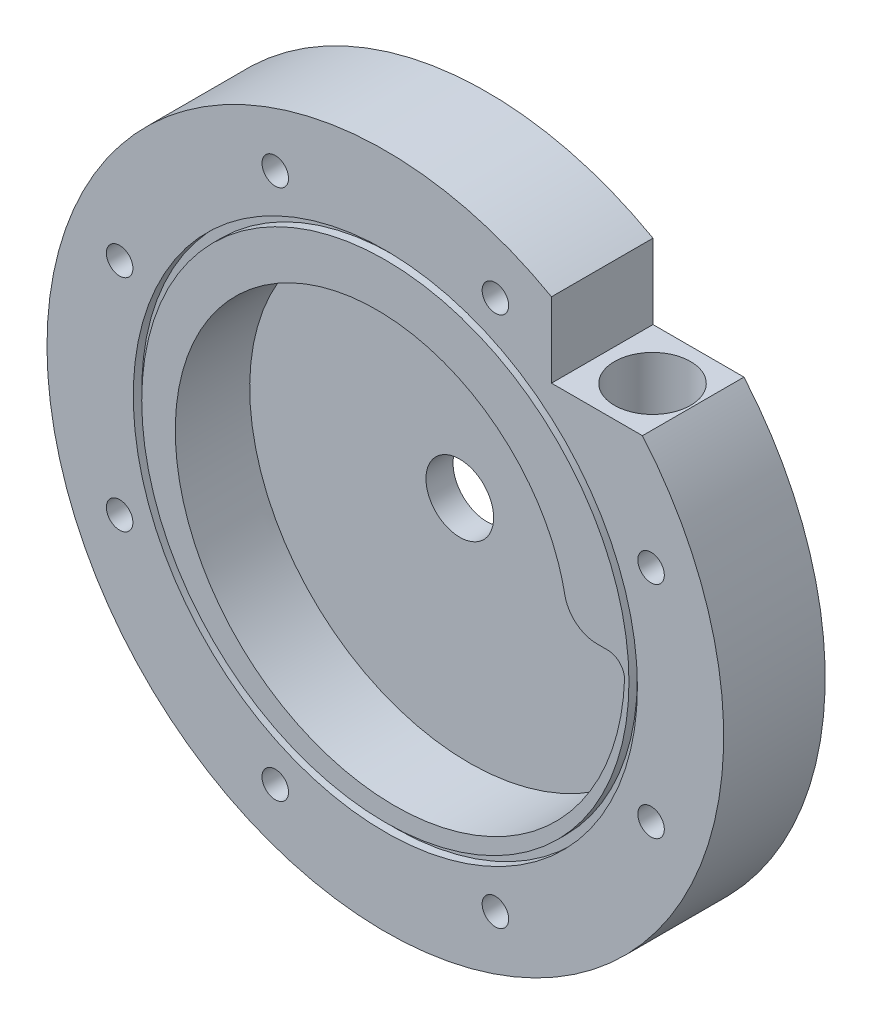
SolidWorks part; units mm, degrees
note: The reader was unsure of these and kept them because the rebuilt part matched: shared geometry of "Sketch1<3>".
material "6061-T6 (SS)"
ref_plane "Front Plane" through (0, 0, 0) normal (0, 0, 1) x (1, 0, 0)
ref_plane "Top Plane" through (0, 0, 0) normal (0, 1, 0) x (1, 0, 0)
ref_plane "Right Plane" through (0, 0, 0) normal (1, 0, 0) x (0, 0, -1)
curve "Volute Spiral"
sketch "Sketch1" plane through (0, 0, 0) normal (0, 0, 1) x (1, 0, 0)
  line L3 (39.6934, 3.175) -> (41.7237, 3.175)
  circle A0 centre (0, 0) radius 63.5
  arc A1 (36.5184, 0) -> (39.6934, 3.175) centre (39.6934, 0) cw
  arc A2 (41.7237, 3.175) -> (44.8987, 0) centre (41.7237, 0) cw
  circle A3 centre (0, 0) radius 6.35
  arc A4 (34.2959, 0) -> (36.5184, 0) centre (35.4071, 0) ccw
  spline S0 degree 3 poles (2030.2227, -117.7395) (22.7858, -27.2351) (33.8418, -13.6396) (34.312, 0.4316) (34.3179, 0.6476) (34.3271, 1.0799) (34.3329, 2.0903) (34.2799, 3.6074) (34.1204, 5.4103) (33.8802, 7.1353) (33.5529, 8.8499) (33.139, 10.5497) (32.6391, 12.2303) (32.0542, 13.8874) (31.3852, 15.5166) (30.6335, 17.1136) (29.8006, 18.6744) (28.8882, 20.1947) (27.8984, 21.6706) (26.8332, 23.098) (25.6951, 24.4731) (24.4865, 25.7922) (23.2102, 27.0516) (21.8693, 28.248) (20.4667, 29.3779) (19.0058, 30.4382) (17.49, 31.4258) (15.9229, 32.338) (14.3083, 33.1721) (12.6501, 33.9256) (10.9523, 34.5962) (9.219, 35.1819) (7.4546, 35.6807) (5.6632, 36.091) (3.8495, 36.4113) (2.0178, 36.6406) (0.1728, 36.7776) (-1.6809, 36.8217) (-3.5386, 36.7724) (-5.3955, 36.6294) (-7.2471, 36.3925) (-9.0884, 36.0621) (-10.9149, 35.6384) (-12.7217, 35.1223) (-14.5042, 34.5145) (-16.2577, 33.8162) (-17.9777, 33.0288) (-19.6596, 32.1539) (-21.2989, 31.1934) (-22.8914, 30.1492) (-24.4326, 29.0238) (-25.9186, 27.8195) (-27.3451, 26.5392) (-28.7085, 25.1857) (-30.0048, 23.7622) (-31.2305, 22.2719) (-32.3822, 20.7185) (-33.4566, 19.1055) (-34.4506, 17.4368) (-35.3613, 15.7165) (-36.1861, 13.9486) (-36.9225, 12.1375) (-37.5682, 10.2875) (-38.1211, 8.4034) (-38.5795, 6.4896) (-38.9418, 4.5509) (-39.2066, 2.5922) (-39.3728, 0.6184) (-39.4396, -1.3656) (-39.4064, -3.3547) (-39.2728, -5.3439) (-39.0387, -7.3282) (-38.7043, -9.3025) (-38.27, -11.2616) (-37.7365, -13.2006) (-37.1047, -15.1144) (-36.3758, -16.9979) (-35.5512, -18.8464) (-34.6327, -20.6549) (-33.6221, -22.4187) (-32.5217, -24.133) (-31.3338, -25.7933) (-30.0611, -27.3951) (-28.7065, -28.9341) (-27.273, -30.4061) (-25.7641, -31.807) (-24.1833, -33.133) (-22.5341, -34.3804) (-20.8206, -35.5457) (-19.0469, -36.6255) (-17.2172, -37.6168) (-15.3359, -38.5166) (-13.4077, -39.3222) (-11.4371, -40.0312) (-9.4292, -40.6415) (-7.3888, -41.1509) (-5.3209, -41.5579) (-3.2309, -41.8608) (-1.1238, -42.0586) (0.9951, -42.1502) (3.1203, -42.135) (5.2464, -42.0126) (7.3682, -41.7828) (9.4801, -41.4458) (11.5767, -41.002) (13.6527, -40.4521) (15.7025, -39.7969) (17.721, -39.0379) (19.7028, -38.1764) (21.6428, -37.2142) (23.5358, -36.1534) (25.3768, -34.9962) (27.1608, -33.7453) (28.8832, -32.4033) (30.5392, -30.9734) (32.1244, -29.4588) (33.6345, -27.8631) (35.0652, -26.19) (36.4127, -24.4433) (37.6731, -22.6273) (38.8428, -20.7464) (39.9186, -18.8049) (40.8973, -16.8077) (41.776, -14.7596) (42.552, -12.6656) (43.223, -10.5308) (43.7868, -8.3606) (44.2416, -6.1602) (44.5713, -4.0283) (44.7406, -2.4408) (44.8137, -1.5038) (44.8395, -1.1283) (44.857, -0.8465) (44.8728, -0.5645) (45.7077, 16.1379) (34.8318, 33.2748) (2044.1391, -40.8845) knots -0.167612 -0.167612 -0.167612 -0.167612 0.00087 0.001741 0.002611 0.003482 0.006969 0.014827 0.021828 0.028845 0.035878 0.042927 0.049991 0.057071 0.064166 0.071278 0.078405 0.085549 0.092709 0.099884 0.107076 0.114284 0.121508 0.128748 0.136004 0.143277 0.150566 0.157872 0.165193 0.172531 0.179886 0.187257 0.194645 0.202049 0.209469 0.216906 0.22436 0.231831 0.239318 0.246821 0.254342 0.261879 0.269433 0.277004 0.284591 0.292196 0.299817 0.307455 0.31511 0.322782 0.330471 0.338177 0.3459 0.35364 0.361397 0.369171 0.376962 0.38477 0.392595 0.400438 0.408298 0.416174 0.424069 0.43198 0.439908 0.447854 0.455817 0.463798 0.471796 0.479811 0.487843 0.495893 0.503961 0.512046 0.520148 0.528268 0.536405 0.54456 0.552732 0.560922 0.569129 0.577354 0.585596 0.593857 0.602135 0.61043 0.618743 0.627074 0.635423 0.643789 0.652173 0.660575 0.668994 0.677432 0.685887 0.69436 0.702851 0.71136 0.719886 0.728431 0.736993 0.745574 0.754172 0.762788 0.771423 0.780075 0.788745 0.797433 0.80614 0.814864 0.823607 0.832367 0.841146 0.849943 0.858758 0.867591 0.876443 0.885312 0.8942 0.903106 0.91203 0.920973 0.929933 0.938912 0.94791 0.956925 0.965959 0.975011 0.984082 0.992034 0.994309 0.995446 0.996584 0.997723 0.998861 1.198776 1.198776 1.198776 1.198776 only from (34.2959, 0) to (44.8987, 0) construction
  spline S1 degree 3 poles (34.2959, 0) (34.2988, 0.0719) (34.3048, 0.2158) (34.312, 0.4316) (34.3179, 0.6476) (34.3271, 1.0799) (34.3329, 2.0903) (34.2799, 3.6074) (34.1204, 5.4103) (33.8802, 7.1353) (33.5529, 8.8499) (33.139, 10.5497) (32.6391, 12.2303) (32.0542, 13.8874) (31.3852, 15.5166) (30.6335, 17.1136) (29.8006, 18.6744) (28.8882, 20.1947) (27.8984, 21.6706) (26.8332, 23.098) (25.6951, 24.4731) (24.4865, 25.7922) (23.2102, 27.0516) (21.8693, 28.248) (20.4667, 29.3779) (19.0058, 30.4382) (17.49, 31.4258) (15.9229, 32.338) (14.3083, 33.1721) (12.6501, 33.9256) (10.9523, 34.5962) (9.219, 35.1819) (7.4546, 35.6807) (5.6632, 36.091) (3.8495, 36.4113) (2.0178, 36.6406) (0.1728, 36.7776) (-1.6809, 36.8217) (-3.5386, 36.7724) (-5.3955, 36.6294) (-7.2471, 36.3925) (-9.0884, 36.0621) (-10.9149, 35.6384) (-12.7217, 35.1223) (-14.5042, 34.5145) (-16.2577, 33.8162) (-17.9777, 33.0288) (-19.6596, 32.1539) (-21.2989, 31.1934) (-22.8914, 30.1492) (-24.4326, 29.0238) (-25.9186, 27.8195) (-27.3451, 26.5392) (-28.7085, 25.1857) (-30.0048, 23.7622) (-31.2305, 22.2719) (-32.3822, 20.7185) (-33.4566, 19.1055) (-34.4506, 17.4368) (-35.3613, 15.7165) (-36.1861, 13.9486) (-36.9225, 12.1375) (-37.5682, 10.2875) (-38.1211, 8.4034) (-38.5795, 6.4896) (-38.9418, 4.5509) (-39.2066, 2.5922) (-39.3728, 0.6184) (-39.4396, -1.3656) (-39.4064, -3.3547) (-39.2728, -5.3439) (-39.0387, -7.3282) (-38.7043, -9.3025) (-38.27, -11.2616) (-37.7365, -13.2006) (-37.1047, -15.1144) (-36.3758, -16.9979) (-35.5512, -18.8464) (-34.6327, -20.6549) (-33.6221, -22.4187) (-32.5217, -24.133) (-31.3338, -25.7933) (-30.0611, -27.3951) (-28.7065, -28.9341) (-27.273, -30.4061) (-25.7641, -31.807) (-24.1833, -33.133) (-22.5341, -34.3804) (-20.8206, -35.5457) (-19.0469, -36.6255) (-17.2172, -37.6168) (-15.3359, -38.5166) (-13.4077, -39.3222) (-11.4371, -40.0312) (-9.4292, -40.6415) (-7.3888, -41.1509) (-5.3209, -41.5579) (-3.2309, -41.8608) (-1.1238, -42.0586) (0.9951, -42.1502) (3.1203, -42.135) (5.2464, -42.0126) (7.3682, -41.7828) (9.4801, -41.4458) (11.5767, -41.002) (13.6527, -40.4521) (15.7025, -39.7969) (17.721, -39.0379) (19.7028, -38.1764) (21.6428, -37.2142) (23.5358, -36.1534) (25.3768, -34.9962) (27.1608, -33.7453) (28.8832, -32.4033) (30.5392, -30.9734) (32.1244, -29.4588) (33.6345, -27.8631) (35.0652, -26.19) (36.4127, -24.4433) (37.6731, -22.6273) (38.8428, -20.7464) (39.9186, -18.8049) (40.8973, -16.8077) (41.776, -14.7596) (42.552, -12.6656) (43.223, -10.5308) (43.7868, -8.3606) (44.2416, -6.1602) (44.5713, -4.0283) (44.7406, -2.4408) (44.8137, -1.5038) (44.8395, -1.1283) (44.857, -0.8465) (44.8728, -0.5645) (44.8869, -0.2823) (44.8948, -0.0941) (44.8987, 0) knots 0 0 0 0 0.00087 0.001741 0.002611 0.003482 0.006969 0.014827 0.021828 0.028845 0.035878 0.042927 0.049991 0.057071 0.064166 0.071278 0.078405 0.085549 0.092709 0.099884 0.107076 0.114284 0.121508 0.128748 0.136004 0.143277 0.150566 0.157872 0.165193 0.172531 0.179886 0.187257 0.194645 0.202049 0.209469 0.216906 0.22436 0.231831 0.239318 0.246821 0.254342 0.261879 0.269433 0.277004 0.284591 0.292196 0.299817 0.307455 0.31511 0.322782 0.330471 0.338177 0.3459 0.35364 0.361397 0.369171 0.376962 0.38477 0.392595 0.400438 0.408298 0.416174 0.424069 0.43198 0.439908 0.447854 0.455817 0.463798 0.471796 0.479811 0.487843 0.495893 0.503961 0.512046 0.520148 0.528268 0.536405 0.54456 0.552732 0.560922 0.569129 0.577354 0.585596 0.593857 0.602135 0.61043 0.618743 0.627074 0.635423 0.643789 0.652173 0.660575 0.668994 0.677432 0.685887 0.69436 0.702851 0.71136 0.719886 0.728431 0.736993 0.745574 0.754172 0.762788 0.771423 0.780075 0.788745 0.797433 0.80614 0.814864 0.823607 0.832367 0.841146 0.849943 0.858758 0.867591 0.876443 0.885312 0.8942 0.903106 0.91203 0.920973 0.929933 0.938912 0.94791 0.956925 0.965959 0.975011 0.984082 0.992034 0.994309 0.995446 0.996584 0.997723 0.998861 1 1 1 1
  dimension "D2" = 127
  dimension "D3" = 3.175
  dimension "D5" = 12.7
  dimension "D1" = 2.2225
extrude "Walls" add sketch "Sketch1" along normal blind 9.0729
extrude "Floor" add sketch "Sketch1<3>" against normal blind 5.08
sketch "Sketch1<3>" plane through (0, 0, 0) normal (0, 0, 1) x (1, 0, 0) same geometry as "Sketch1"
sketch "Sketch4" plane through (0, 0, -5.08) normal (0, 0, -1) x (-1, 0, 0)
  circle A0 centre (0, 0) radius 63.5
  circle A1 centre (0, 0) radius 60.325
  circle A2 centre (0, 0) radius 63.5 construction
  dimension "D1" = 3.175
ref_plane "Total Thickness" through (0, 0, 13.97) normal (0, 0, -1) x (-1, 0, 0)
sketch "Sketch5" plane through (0, 0, 9.0729) normal (0, 0, 1) x (1, 0, 0)
  line L2 (39.6934, 3.175) -> (41.7237, 3.175) construction
  line L3 (39.6934, 3.175) -> (41.7237, 3.175)
  arc A0 (44.8987, 0) -> (41.7237, 3.175) centre (41.7237, 0) ccw construction
  arc A1 (44.8987, 0) -> (41.7237, 3.175) centre (41.7237, 0) ccw
  arc A2 (33.6876, 8.1232) -> (39.6934, 3.175) centre (39.6934, 9.2938) ccw
  spline S0 degree 3 poles (2030.2227, -117.7395) (22.7858, -27.2351) (33.8418, -13.6396) (34.312, 0.4316) (34.3179, 0.6476) (34.3271, 1.0799) (34.3329, 2.0903) (34.2799, 3.6074) (34.1204, 5.4103) (33.8802, 7.1353) (33.5529, 8.8499) (33.139, 10.5497) (32.6391, 12.2303) (32.0542, 13.8874) (31.3852, 15.5166) (30.6335, 17.1136) (29.8006, 18.6744) (28.8882, 20.1947) (27.8984, 21.6706) (26.8332, 23.098) (25.6951, 24.4731) (24.4865, 25.7922) (23.2102, 27.0516) (21.8693, 28.248) (20.4667, 29.3779) (19.0058, 30.4382) (17.49, 31.4258) (15.9229, 32.338) (14.3083, 33.1721) (12.6501, 33.9256) (10.9523, 34.5962) (9.219, 35.1819) (7.4546, 35.6807) (5.6632, 36.091) (3.8495, 36.4113) (2.0178, 36.6406) (0.1728, 36.7776) (-1.6809, 36.8217) (-3.5386, 36.7724) (-5.3955, 36.6294) (-7.2471, 36.3925) (-9.0884, 36.0621) (-10.9149, 35.6384) (-12.7217, 35.1223) (-14.5042, 34.5145) (-16.2577, 33.8162) (-17.9777, 33.0288) (-19.6596, 32.1539) (-21.2989, 31.1934) (-22.8914, 30.1492) (-24.4326, 29.0238) (-25.9186, 27.8195) (-27.3451, 26.5392) (-28.7085, 25.1857) (-30.0048, 23.7622) (-31.2305, 22.2719) (-32.3822, 20.7185) (-33.4566, 19.1055) (-34.4506, 17.4368) (-35.3613, 15.7165) (-36.1861, 13.9486) (-36.9225, 12.1375) (-37.5682, 10.2875) (-38.1211, 8.4034) (-38.5795, 6.4896) (-38.9418, 4.5509) (-39.2066, 2.5922) (-39.3728, 0.6184) (-39.4396, -1.3656) (-39.4064, -3.3547) (-39.2728, -5.3439) (-39.0387, -7.3282) (-38.7043, -9.3025) (-38.27, -11.2616) (-37.7365, -13.2006) (-37.1047, -15.1144) (-36.3758, -16.9979) (-35.5512, -18.8464) (-34.6327, -20.6549) (-33.6221, -22.4187) (-32.5217, -24.133) (-31.3338, -25.7933) (-30.0611, -27.3951) (-28.7065, -28.9341) (-27.273, -30.4061) (-25.7641, -31.807) (-24.1833, -33.133) (-22.5341, -34.3804) (-20.8206, -35.5457) (-19.0469, -36.6255) (-17.2172, -37.6168) (-15.3359, -38.5166) (-13.4077, -39.3222) (-11.4371, -40.0312) (-9.4292, -40.6415) (-7.3888, -41.1509) (-5.3209, -41.5579) (-3.2309, -41.8608) (-1.1238, -42.0586) (0.9951, -42.1502) (3.1203, -42.135) (5.2464, -42.0126) (7.3682, -41.7828) (9.4801, -41.4458) (11.5767, -41.002) (13.6527, -40.4521) (15.7025, -39.7969) (17.721, -39.0379) (19.7028, -38.1764) (21.6428, -37.2142) (23.5358, -36.1534) (25.3768, -34.9962) (27.1608, -33.7453) (28.8832, -32.4033) (30.5392, -30.9734) (32.1244, -29.4588) (33.6345, -27.8631) (35.0652, -26.19) (36.4127, -24.4433) (37.6731, -22.6273) (38.8428, -20.7464) (39.9186, -18.8049) (40.8973, -16.8077) (41.776, -14.7596) (42.552, -12.6656) (43.223, -10.5308) (43.7868, -8.3606) (44.2416, -6.1602) (44.5713, -4.0283) (44.7406, -2.4408) (44.8137, -1.5038) (44.8395, -1.1283) (44.857, -0.8465) (44.8728, -0.5645) (45.7077, 16.1379) (34.8318, 33.2748) (2044.1391, -40.8845) knots -0.167612 -0.167612 -0.167612 -0.167612 0.00087 0.001741 0.002611 0.003482 0.006969 0.014827 0.021828 0.028845 0.035878 0.042927 0.049991 0.057071 0.064166 0.071278 0.078405 0.085549 0.092709 0.099884 0.107076 0.114284 0.121508 0.128748 0.136004 0.143277 0.150566 0.157872 0.165193 0.172531 0.179886 0.187257 0.194645 0.202049 0.209469 0.216906 0.22436 0.231831 0.239318 0.246821 0.254342 0.261879 0.269433 0.277004 0.284591 0.292196 0.299817 0.307455 0.31511 0.322782 0.330471 0.338177 0.3459 0.35364 0.361397 0.369171 0.376962 0.38477 0.392595 0.400438 0.408298 0.416174 0.424069 0.43198 0.439908 0.447854 0.455817 0.463798 0.471796 0.479811 0.487843 0.495893 0.503961 0.512046 0.520148 0.528268 0.536405 0.54456 0.552732 0.560922 0.569129 0.577354 0.585596 0.593857 0.602135 0.61043 0.618743 0.627074 0.635423 0.643789 0.652173 0.660575 0.668994 0.677432 0.685887 0.69436 0.702851 0.71136 0.719886 0.728431 0.736993 0.745574 0.754172 0.762788 0.771423 0.780075 0.788745 0.797433 0.80614 0.814864 0.823607 0.832367 0.841146 0.849943 0.858758 0.867591 0.876443 0.885312 0.8942 0.903106 0.91203 0.920973 0.929933 0.938912 0.94791 0.956925 0.965959 0.975011 0.984082 0.992034 0.994309 0.995446 0.996584 0.997723 0.998861 1.198776 1.198776 1.198776 1.198776 only from (34.2959, 0) to (44.8987, 0) construction
  spline S1 degree 3 poles (34.2959, 0) (34.2988, 0.0719) (34.3048, 0.2158) (34.312, 0.4316) (34.3179, 0.6476) (34.3271, 1.0799) (34.3329, 2.0903) (34.2799, 3.6074) (34.1204, 5.4103) (33.8802, 7.1353) (33.5529, 8.8499) (33.139, 10.5497) (32.6391, 12.2303) (32.0542, 13.8874) (31.3852, 15.5166) (30.6335, 17.1136) (29.8006, 18.6744) (28.8882, 20.1947) (27.8984, 21.6706) (26.8332, 23.098) (25.6951, 24.4731) (24.4865, 25.7922) (23.2102, 27.0516) (21.8693, 28.248) (20.4667, 29.3779) (19.0058, 30.4382) (17.49, 31.4258) (15.9229, 32.338) (14.3083, 33.1721) (12.6501, 33.9256) (10.9523, 34.5962) (9.219, 35.1819) (7.4546, 35.6807) (5.6632, 36.091) (3.8495, 36.4113) (2.0178, 36.6406) (0.1728, 36.7776) (-1.6809, 36.8217) (-3.5386, 36.7724) (-5.3955, 36.6294) (-7.2471, 36.3925) (-9.0884, 36.0621) (-10.9149, 35.6384) (-12.7217, 35.1223) (-14.5042, 34.5145) (-16.2577, 33.8162) (-17.9777, 33.0288) (-19.6596, 32.1539) (-21.2989, 31.1934) (-22.8914, 30.1492) (-24.4326, 29.0238) (-25.9186, 27.8195) (-27.3451, 26.5392) (-28.7085, 25.1857) (-30.0048, 23.7622) (-31.2305, 22.2719) (-32.3822, 20.7185) (-33.4566, 19.1055) (-34.4506, 17.4368) (-35.3613, 15.7165) (-36.1861, 13.9486) (-36.9225, 12.1375) (-37.5682, 10.2875) (-38.1211, 8.4034) (-38.5795, 6.4896) (-38.9418, 4.5509) (-39.2066, 2.5922) (-39.3728, 0.6184) (-39.4396, -1.3656) (-39.4064, -3.3547) (-39.2728, -5.3439) (-39.0387, -7.3282) (-38.7043, -9.3025) (-38.27, -11.2616) (-37.7365, -13.2006) (-37.1047, -15.1144) (-36.3758, -16.9979) (-35.5512, -18.8464) (-34.6327, -20.6549) (-33.6221, -22.4187) (-32.5217, -24.133) (-31.3338, -25.7933) (-30.0611, -27.3951) (-28.7065, -28.9341) (-27.273, -30.4061) (-25.7641, -31.807) (-24.1833, -33.133) (-22.5341, -34.3804) (-20.8206, -35.5457) (-19.0469, -36.6255) (-17.2172, -37.6168) (-15.3359, -38.5166) (-13.4077, -39.3222) (-11.4371, -40.0312) (-9.4292, -40.6415) (-7.3888, -41.1509) (-5.3209, -41.5579) (-3.2309, -41.8608) (-1.1238, -42.0586) (0.9951, -42.1502) (3.1203, -42.135) (5.2464, -42.0126) (7.3682, -41.7828) (9.4801, -41.4458) (11.5767, -41.002) (13.6527, -40.4521) (15.7025, -39.7969) (17.721, -39.0379) (19.7028, -38.1764) (21.6428, -37.2142) (23.5358, -36.1534) (25.3768, -34.9962) (27.1608, -33.7453) (28.8832, -32.4033) (30.5392, -30.9734) (32.1244, -29.4588) (33.6345, -27.8631) (35.0652, -26.19) (36.4127, -24.4433) (37.6731, -22.6273) (38.8428, -20.7464) (39.9186, -18.8049) (40.8973, -16.8077) (41.776, -14.7596) (42.552, -12.6656) (43.223, -10.5308) (43.7868, -8.3606) (44.2416, -6.1602) (44.5713, -4.0283) (44.7406, -2.4408) (44.8137, -1.5038) (44.8395, -1.1283) (44.857, -0.8465) (44.8728, -0.5645) (44.8869, -0.2823) (44.8948, -0.0941) (44.8987, 0) knots 0 0 0 0 0.00087 0.001741 0.002611 0.003482 0.006969 0.014827 0.021828 0.028845 0.035878 0.042927 0.049991 0.057071 0.064166 0.071278 0.078405 0.085549 0.092709 0.099884 0.107076 0.114284 0.121508 0.128748 0.136004 0.143277 0.150566 0.157872 0.165193 0.172531 0.179886 0.187257 0.194645 0.202049 0.209469 0.216906 0.22436 0.231831 0.239318 0.246821 0.254342 0.261879 0.269433 0.277004 0.284591 0.292196 0.299817 0.307455 0.31511 0.322782 0.330471 0.338177 0.3459 0.35364 0.361397 0.369171 0.376962 0.38477 0.392595 0.400438 0.408298 0.416174 0.424069 0.43198 0.439908 0.447854 0.455817 0.463798 0.471796 0.479811 0.487843 0.495893 0.503961 0.512046 0.520148 0.528268 0.536405 0.54456 0.552732 0.560922 0.569129 0.577354 0.585596 0.593857 0.602135 0.61043 0.618743 0.627074 0.635423 0.643789 0.652173 0.660575 0.668994 0.677432 0.685887 0.69436 0.702851 0.71136 0.719886 0.728431 0.736993 0.745574 0.754172 0.762788 0.771423 0.780075 0.788745 0.797433 0.80614 0.814864 0.823607 0.832367 0.841146 0.849943 0.858758 0.867591 0.876443 0.885312 0.8942 0.903106 0.91203 0.920973 0.929933 0.938912 0.94791 0.956925 0.965959 0.975011 0.984082 0.992034 0.994309 0.995446 0.996584 0.997723 0.998861 1 1 1 1
  spline S2 degree 3 poles (34.2959, 0) (34.2988, 0.0719) (34.3048, 0.2158) (34.312, 0.4316) (34.3179, 0.6476) (34.3271, 1.0799) (34.3329, 2.0903) (34.2799, 3.6074) (34.1204, 5.4103) (33.8802, 7.1353) (33.5529, 8.8499) (33.139, 10.5497) (32.6391, 12.2303) (32.0542, 13.8874) (31.3852, 15.5166) (30.6335, 17.1136) (29.8006, 18.6744) (28.8882, 20.1947) (27.8984, 21.6706) (26.8332, 23.098) (25.6951, 24.4731) (24.4865, 25.7922) (23.2102, 27.0516) (21.8693, 28.248) (20.4667, 29.3779) (19.0058, 30.4382) (17.49, 31.4258) (15.9229, 32.338) (14.3083, 33.1721) (12.6501, 33.9256) (10.9523, 34.5962) (9.219, 35.1819) (7.4546, 35.6807) (5.6632, 36.091) (3.8495, 36.4113) (2.0178, 36.6406) (0.1728, 36.7776) (-1.6809, 36.8217) (-3.5386, 36.7724) (-5.3955, 36.6294) (-7.2471, 36.3925) (-9.0884, 36.0621) (-10.9149, 35.6384) (-12.7217, 35.1223) (-14.5042, 34.5145) (-16.2577, 33.8162) (-17.9777, 33.0288) (-19.6596, 32.1539) (-21.2989, 31.1934) (-22.8914, 30.1492) (-24.4326, 29.0238) (-25.9186, 27.8195) (-27.3451, 26.5392) (-28.7085, 25.1857) (-30.0048, 23.7622) (-31.2305, 22.2719) (-32.3822, 20.7185) (-33.4566, 19.1055) (-34.4506, 17.4368) (-35.3613, 15.7165) (-36.1861, 13.9486) (-36.9225, 12.1375) (-37.5682, 10.2875) (-38.1211, 8.4034) (-38.5795, 6.4896) (-38.9418, 4.5509) (-39.2066, 2.5922) (-39.3728, 0.6184) (-39.4396, -1.3656) (-39.4064, -3.3547) (-39.2728, -5.3439) (-39.0387, -7.3282) (-38.7043, -9.3025) (-38.27, -11.2616) (-37.7365, -13.2006) (-37.1047, -15.1144) (-36.3758, -16.9979) (-35.5512, -18.8464) (-34.6327, -20.6549) (-33.6221, -22.4187) (-32.5217, -24.133) (-31.3338, -25.7933) (-30.0611, -27.3951) (-28.7065, -28.9341) (-27.273, -30.4061) (-25.7641, -31.807) (-24.1833, -33.133) (-22.5341, -34.3804) (-20.8206, -35.5457) (-19.0469, -36.6255) (-17.2172, -37.6168) (-15.3359, -38.5166) (-13.4077, -39.3222) (-11.4371, -40.0312) (-9.4292, -40.6415) (-7.3888, -41.1509) (-5.3209, -41.5579) (-3.2309, -41.8608) (-1.1238, -42.0586) (0.9951, -42.1502) (3.1203, -42.135) (5.2464, -42.0126) (7.3682, -41.7828) (9.4801, -41.4458) (11.5767, -41.002) (13.6527, -40.4521) (15.7025, -39.7969) (17.721, -39.0379) (19.7028, -38.1764) (21.6428, -37.2142) (23.5358, -36.1534) (25.3768, -34.9962) (27.1608, -33.7453) (28.8832, -32.4033) (30.5392, -30.9734) (32.1244, -29.4588) (33.6345, -27.8631) (35.0652, -26.19) (36.4127, -24.4433) (37.6731, -22.6273) (38.8428, -20.7464) (39.9186, -18.8049) (40.8973, -16.8077) (41.776, -14.7596) (42.552, -12.6656) (43.223, -10.5308) (43.7868, -8.3606) (44.2416, -6.1602) (44.5713, -4.0283) (44.7406, -2.4408) (44.8137, -1.5038) (44.8395, -1.1283) (44.857, -0.8465) (44.8728, -0.5645) (44.8869, -0.2823) (44.8948, -0.0941) (44.8987, 0) knots 0 0 0 0 0.00087 0.001741 0.002611 0.003482 0.006969 0.014827 0.021828 0.028845 0.035878 0.042927 0.049991 0.057071 0.064166 0.071278 0.078405 0.085549 0.092709 0.099884 0.107076 0.114284 0.121508 0.128748 0.136004 0.143277 0.150566 0.157872 0.165193 0.172531 0.179886 0.187257 0.194645 0.202049 0.209469 0.216906 0.22436 0.231831 0.239318 0.246821 0.254342 0.261879 0.269433 0.277004 0.284591 0.292196 0.299817 0.307455 0.31511 0.322782 0.330471 0.338177 0.3459 0.35364 0.361397 0.369171 0.376962 0.38477 0.392595 0.400438 0.408298 0.416174 0.424069 0.43198 0.439908 0.447854 0.455817 0.463798 0.471796 0.479811 0.487843 0.495893 0.503961 0.512046 0.520148 0.528268 0.536405 0.54456 0.552732 0.560922 0.569129 0.577354 0.585596 0.593857 0.602135 0.61043 0.618743 0.627074 0.635423 0.643789 0.652173 0.660575 0.668994 0.677432 0.685887 0.69436 0.702851 0.71136 0.719886 0.728431 0.736993 0.745574 0.754172 0.762788 0.771423 0.780075 0.788745 0.797433 0.80614 0.814864 0.823607 0.832367 0.841146 0.849943 0.858758 0.867591 0.876443 0.885312 0.8942 0.903106 0.91203 0.920973 0.929933 0.938912 0.94791 0.956925 0.965959 0.975011 0.984082 0.992034 0.994309 0.995446 0.996584 0.997723 0.998861 1 1 1 1 construction
extrude "Ceiling Constraint" add sketch "Sketch5" along normal up to surface (4.8971 mm away) up to plane "Total Thickness"
ref_plane "Outlet Plane" through (0, 41.275, 0) normal (0, -1, 0) x (-1, 0, 0)
sketch "Sketch7" plane through (0, 41.275, 0) normal (0, -1, 0) x (-1, 0, 0)
  line L0 (-48.2558, -13.97) -> (-31.1836, -13.97)
  line L1 (-31.1836, -13.97) -> (-31.1836, 5.08)
  line L2 (-31.1836, 5.08) -> (-48.2558, 5.08)
  line L3 (-48.2558, 5.08) -> (-48.2558, -13.97)
  line L4 (-39.6934, -9.0729) -> (-39.6934, 0) construction
  line L5 (-39.6934, -9.0729) -> (-39.6934, 0) construction
  line L6 (-39.6934, 0) -> (-41.7237, 0) construction
  line L7 (-39.6934, 0) -> (-41.7237, 0) construction
  line L8 (-39.6934, -9.0729) -> (-41.7237, 0) construction
  line L16 (-39.6934, -13.97) -> (-33.6876, -13.97) construction
  point P11 (-40.7086, -4.5364)
  dimension "D1" = 9.525
extrude "Outlet Cut" cut sketch "Sketch7" against normal through all
hole_wizard "Outlet Hole" positions "3DSketch2" profile "Sketch20" hole size "3/8" standard "ANSI Inch"
sketch3d "3DSketch2"
  line L0 (41.7237, 3.175, 0) -> (39.6934, 3.175, 9.0729) construction
  point P0 (40.7086, 41.275, 4.5364)
  point P11 (40.7086, 3.175, 4.5364)
sketch "Sketch20" plane through (40.7086, 41.275, 4.5364) normal (1, 0, 0) x (0, 0, 1)
  line L0 (0, 0) -> (0, 43.5016)
  line L1 (0, 43.5016) -> (4.7625, 40.64)
  line L2 (4.7625, 40.64) -> (4.7625, 0)
  line L5 (4.7625, 0) -> (0, 0)
  line L10 (0, 43.5016) -> (-4.7625, 40.64) construction
  line L11 (0, -6.35) -> (0, 107.95) construction
  dimension "Hole Dia." = 9.525
  dimension "Hole Depth" = 40.64
  dimension "Drill Angle" = 118
hole_wizard "Pipe Tap Drill for 3/8 Tap1" positions "Sketch9" profile "Sketch11" hole size "3/8" standard "ANSI Inch"
sketch "Sketch9" plane through (0, 41.275, 0) normal (0, 1, 0) x (1, 0, 0)
  line L8 (48.2558, -13.97) -> (48.2558, 5.08)
  line L9 (48.2558, 5.08) -> (31.1836, 5.08)
  line L10 (31.1836, 5.08) -> (31.1836, -13.97)
  line L12 (48.2558, -13.97) -> (48.2558, 5.08)
  line L13 (48.2558, 5.08) -> (31.1836, 5.08)
  line L14 (31.1836, 5.08) -> (31.1836, -13.97)
  line L34 (31.1836, -13.97) -> (48.2558, -13.97)
  line L35 (31.1836, -13.97) -> (48.2558, -13.97)
  point P0 (40.7086, -4.5364)
  dimension "D1" = 0
sketch "Sketch11" plane through (40.7086, 41.275, 4.5364) normal (1, 0, 0) x (0, 0, 1)
  line L0 (0, 0) -> (0, 16.9886)
  line L1 (0, 16.9886) -> (7.1374, 12.7)
  line L2 (7.1374, 12.7) -> (7.1374, 0)
  line L5 (7.1374, 0) -> (0, 0)
  line L10 (0, 16.9886) -> (-7.1374, 12.7) construction
  line L11 (0, -6.35) -> (0, 107.95) construction
  dimension "Hole Dia." = 14.2748
  dimension "Hole Depth" = 12.7
  dimension "Drill Angle" = 118
sketch "Sketch16" plane through (0, 0, 13.97) normal (0, 0, 1) x (1, 0, 0)
  circle A0 centre (0, 0) radius 45.72
  circle A1 centre (0, 0) radius 47.3075
  dimension "D1" = 91.44
  dimension "D2" = 1.5875
extrude "Seal Groove" cut sketch "Sketch16" against normal blind 1.5875
hole_wizard "Fastener Holes" positions "Sketch17" profile "Sketch18" hole size "#10" standard "ANSI Inch" end condition through all
sketch "Sketch17" plane through (0, 0, 13.97) normal (0, 0, 1) x (1, 0, 0)
  line L0 (58.6664, 24.3004) -> (49.8664, 20.6553) construction
  line L2 (0, 0) -> (63.5, 0) construction
  arc A2 (31.1836, 55.3158) -> (48.2558, 41.275) centre (0, 0) ccw construction
  point P0 (49.8664, 20.6553)
  dimension "D1" = 9.525
  dimension "D2" = 22.5
sketch "Sketch18" plane through (49.8664, 20.6553, 13.97) normal (1, 0, 0) x (0, -1, 0)
  line L0 (0, 0) -> (0, 19.05)
  line L1 (0, 19.05) -> (2.4892, 19.05)
  line L2 (2.4892, 19.05) -> (2.4892, 0)
  line L5 (2.4892, 0) -> (0, 0)
  line L11 (0, -6.35) -> (0, 107.95) construction
  dimension "Thru Hole Dia." = 4.9784
  dimension "Thru Hole Depth" = 19.05
pattern_circular "CirPattern1" count 8 over 360 about axis through (0, 0, 0) along (0, 0, 1) of "Fastener Holes"
equation "\"volute_height\"= 0.3572"
equation "\"D1@Walls\"=\"volute_height\""
equation "\"exit_radius\"= 0.2252"
